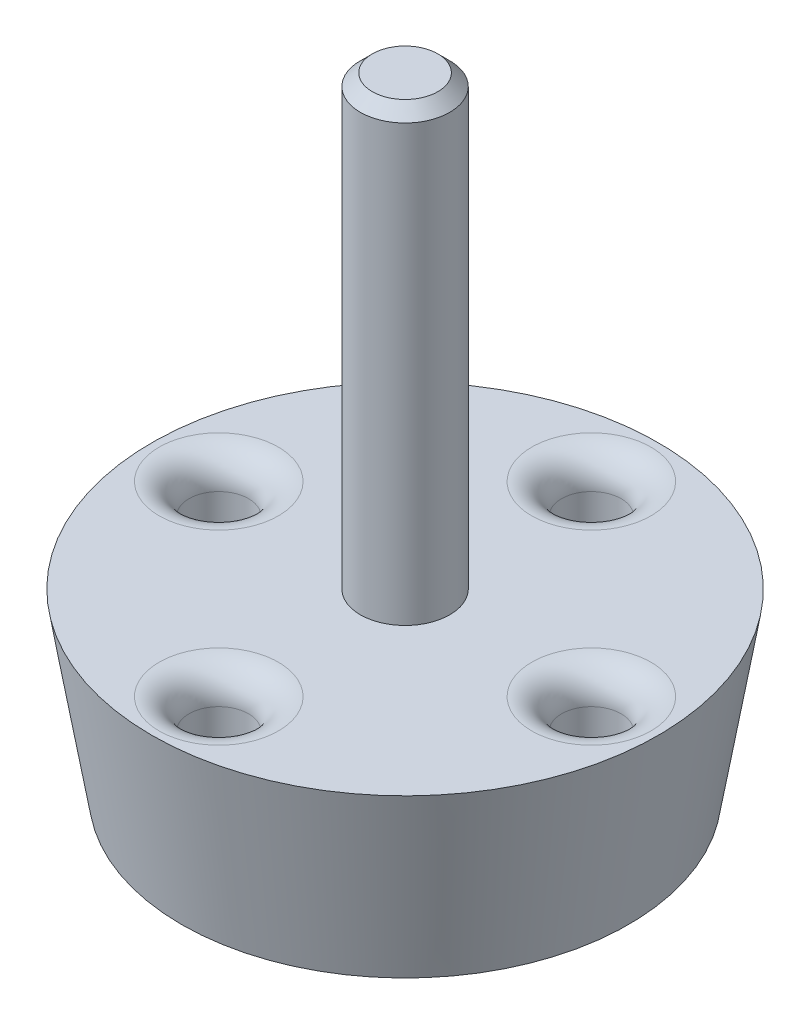
SolidWorks part; units mm, degrees
ref_plane "Front Plane" through (0, 0, 0) normal (0, 0, 1) x (1, 0, 0)
ref_plane "Top Plane" through (0, 0, 0) normal (0, 1, 0) x (1, 0, 0)
ref_plane "Right Plane" through (0, 0, 0) normal (1, 0, 0) x (0, 0, -1)
sketch "Sketch1" plane through (0, 0, 0) normal (0, 1, 0) x (1, 0, 0)
  circle A0 centre (0, 0) radius 7.5
  dimension "D1" = 15
ref_plane "Plane1" through (0, 6, 0) normal (0, 1, 0) x (1, 0, 0)
sketch "Sketch3" plane through (0, 6, 0) normal (0, 1, 0) x (1, 0, 0)
  circle A0 centre (0, 0) radius 8.5
  dimension "D1" = 17
loft "Loft1" add profiles "Sketch3", "Sketch1" connector at (4.7833, 6, 7.0264) connector at (4.4008, 0, 6.0732)
sketch "Sketch4" plane through (0, 6, 0) normal (0, 1, 0) x (1, 0, 0)
  circle A0 centre (0, 0) radius 1.5
  dimension "D1" = 3
extrude "Boss-Extrude1" add sketch "Sketch4" along normal blind 15
sketch "Sketch5" plane through (0, 0, 0) normal (0, -1, 0) x (1, 0, 0)
  circle A0 centre (0, 0) radius 5
  dimension "D1" = 10
extrude "Cut-Extrude1" cut sketch "Sketch5" against normal blind 2
sketch "Sketch6" plane through (0, 0, 0) normal (0, -1, 0) x (1, 0, 0)
  circle A0 centre (0, 6.25) radius 1
  circle A2 centre (6.25, 0) radius 1
  circle A3 centre (0, -6.25) radius 1
  circle A4 centre (-6.25, 0) radius 1
  point P14 (0, 0)
  dimension "D1" = 2
  dimension "D3" = 6.25
  dimension "D2" = 4
extrude "Cut-Extrude4" cut sketch "Sketch6" against normal up to surface (6 mm away) up to face at (0, 6, 1.5)
sketch "Sketch8" plane through (0, 2, 0) normal (0, -1, 0) x (1, 0, 0)
  circle A0 centre (0, 0) radius 1.5
  dimension "D1" = 3
extrude "Cut-Extrude5" cut sketch "Sketch8" against normal blind 1
fillet "Fillet1" radius 1 1 edges at (0, 2, -1.5)
chamfer "Chamfer1" distance 0.4 angle 45 1 edges at (0, 21, 1.5)
fillet "Fillet2" radius 1 4 edges at (-6.25, 6, 1) (0, 6, 7.25) (6.25, 6, 1) (0, 6, -5.25)
